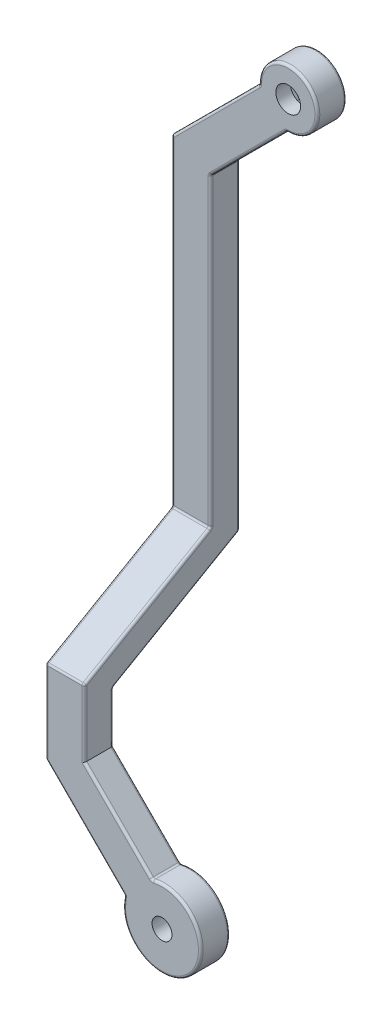
SolidWorks part; units mm, degrees
ref_plane "前视基准面" through (0, 0, 0) normal (0, 0, 1) x (1, 0, 0)
ref_plane "上视基准面" through (0, 0, 0) normal (0, 1, 0) x (1, 0, 0)
ref_plane "右视基准面" through (0, 0, 0) normal (1, 0, 0) x (0, 0, -1)
other "Configuration Table"
sketch "草图1" plane through (0, 0, 0) normal (0, 0, 1) x (1, 0, 0)
  line L0 (0, 0) -> (0, 135) construction
  line L1 (-5.9907, 134.6661) -> (-24, 116.6569)
  line L2 (-24, 116.6569) -> (-24, 18.3431)
  line L3 (-24, 18.3431) -> (-7.7274, 2.0706)
  line L4 (-0.3339, 129.0093) -> (-16, 113.3431)
  line L5 (-16, 113.3431) -> (-16, 21.6569)
  line L6 (-16, 21.6569) -> (-2.0706, 7.7274)
  line L7 (0, 0) -> (-100.097, 0) construction
  line L8 (0, 0) -> (-33.276, 33.276) construction
  line L9 (0, 135) -> (-47.3559, 87.6441) construction
  arc A0 (-0.3339, 129.0093) -> (-5.9907, 134.6661) centre (0, 135) ccw
  arc A1 (-7.7274, 2.0706) -> (-2.0706, 7.7274) centre (0, 0) ccw
  dimension "D2" = 8
  dimension "D4" = 6
  dimension "D1" = 135
  dimension "D3" = 45
  dimension "D5" = 8
  dimension "D6" = 8
  dimension "D7" = 8
  dimension "D8" = 16
  dimension "D9" = 45
extrude "凸台-拉伸1" add sketch "草图1" along normal mid plane 32
ref_axis "下基准轴" through (0, 0, 0) along (0, 0, 1)
ref_axis "上基准轴" through (0, 135, 0) along (0, 0, 1)
sketch "草图2" plane through (0, 0, 16) normal (0, 0, 1) x (1, 0, 0)
  circle A0 centre (0, 0) radius 2.05
  circle A1 centre (0, 135) radius 2.55
  dimension "D1" = 4.1
  dimension "D2" = 5.1
extrude "切除-拉伸1" cut sketch "草图2" against normal through all
sketch "草图4" plane through (0, 0, 0) normal (1, 0, 0) x (0, 0, -1)
  line L0 (16, 141) -> (16, 47.0111) construction
  line L1 (16, 116.6569) -> (16, 18.3431) construction
  line L2 (16, 47.0111) -> (-10, 32)
  line L3 (-10, 32) -> (-10, -8)
  line L4 (-16, -8) -> (16, -8) construction
  line L6 (-16, -8) -> (-16, 35.4641) construction
  line L7 (-16, 116.6569) -> (-16, 18.3431) construction
  line L8 (-16, 35.4641) -> (10, 50.4752)
  line L9 (10, 50.4752) -> (10, 141)
  line L12 (10, 141) -> (-16, 141)
  line L13 (-16, 141) -> (-16, 35.4641)
  line L14 (16, 47.0111) -> (16, -8)
  line L15 (16, -8) -> (-10, -8)
  dimension "D1" = 6
  dimension "D2" = 6
  dimension "D3" = 40
  dimension "D4" = 6
  dimension "D5" = 30
extrude "切除-拉伸2" cut sketch "草图4" against normal through all and the other way through all
sketch "草图5" plane through (0, 0, 10) normal (0, 0, -1) x (-1, 0, 0)
  line L1 (1.5877, -2.75) -> (3.1754, 0)
  line L2 (3.1754, 0) -> (1.5877, 2.75)
  line L3 (1.5877, 2.75) -> (-1.5877, 2.75)
  line L4 (-1.5877, 2.75) -> (-3.1754, 0)
  line L5 (-3.1754, 0) -> (-1.5877, -2.75)
  line L6 (-1.5877, -2.75) -> (1.5877, -2.75)
  circle A0 centre (0, 0) radius 2.75 construction
  dimension "D1" = 5.5
extrude "切除-拉伸3" cut sketch "草图5" against normal blind 3
sketch "草图7" plane through (0, 0, -16) normal (0, 0, -1) x (-1, 0, 0)
  line L1 (3.1754, 135) -> (1.5877, 137.75)
  line L2 (1.5877, 137.75) -> (-1.5877, 137.75)
  line L3 (-1.5877, 137.75) -> (-3.1754, 135)
  line L4 (-3.1754, 135) -> (-1.5877, 132.25)
  line L5 (-1.5877, 132.25) -> (1.5877, 132.25)
  line L6 (1.5877, 132.25) -> (3.1754, 135)
  circle A0 centre (0, 135) radius 2.75 construction
  point P1 (0, 137.75)
  dimension "D1" = 5.5
extrude "切除-拉伸5" cut sketch "草图7" against normal blind 3
fillet "圆角1" radius 0.5 35 edges at (-14.9954, 125.6615, -10) (-15.8637, 10.2068, 16) (-9.0353, 14.6921, 10) (4.2426, 139.2426, -10) (-14.9954, 125.6615, -16) (5.6569, -5.6569, 16) (5.6569, -5.6569, 10) (-24, 25.1716, 10) (-16, 26.8284, 10) (-8.1669, 121.1762, -10) (-16, 42.9697, 3) (-8.1669, 121.1762, -16) (4.2426, 139.2426, -16) (-9.0353, 14.6921, 16) (-15.8637, 10.2068, 10) (-24, 39.5056, -3) (-16, 39.5056, -3) (-16, 81.9092, -10) (-24, 81.834, -16) (-16, 80.1771, -16) (-0.3339, 129.0093, -13) (-16, 113.3431, -13) (-2.0706, 7.7274, 13) (-7.7274, 2.0706, 13) (-20, 47.0111, -16) (-20, 32, 10) (-24, 18.3431, 13) (-20, 35.4641, 16) (-20, 50.4752, -10) (-24, 116.6569, -13) (-5.9907, 134.6661, -13) (-24, 83.566, -10) (-24, 42.9697, 3) (-16, 28.5605, 16) (-24, 26.9036, 16)
